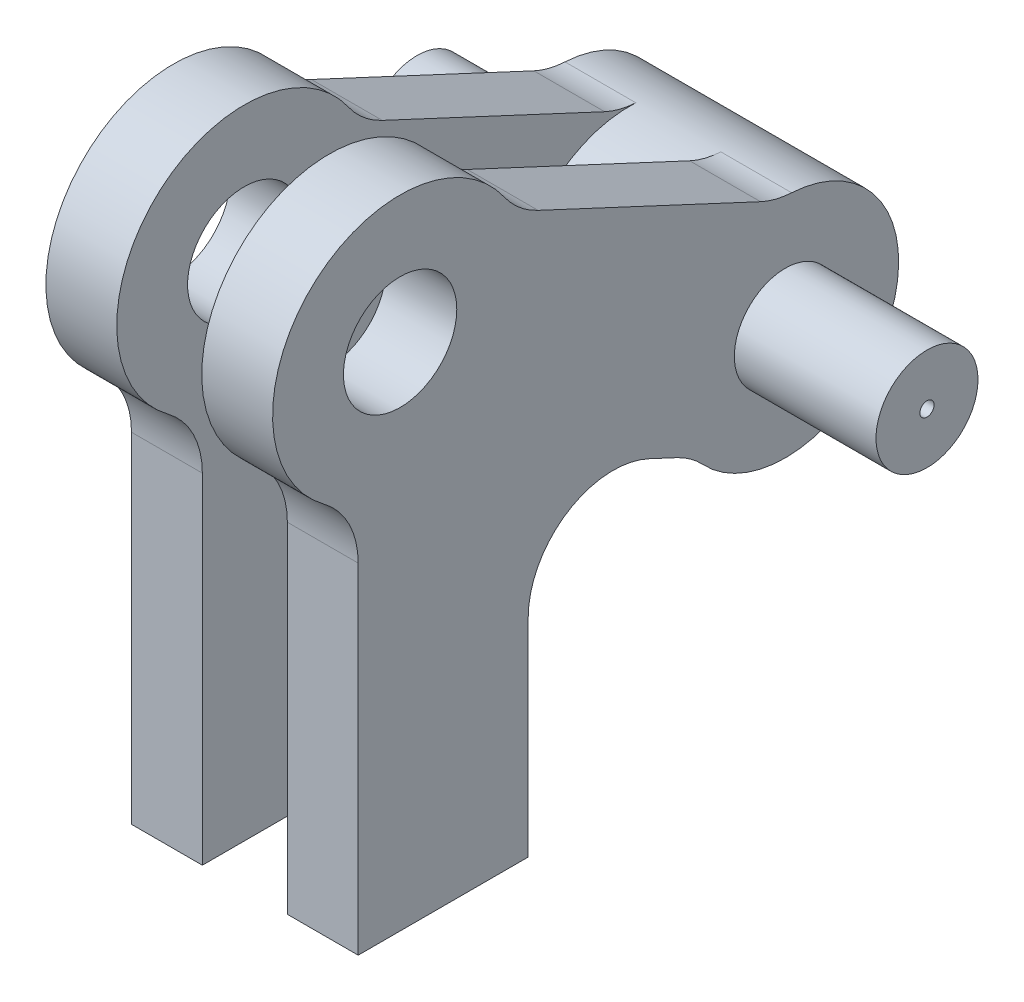
SolidWorks part; units mm, degrees
ref_plane "前视基准面" through (0, 0, 0) normal (0, 0, 1) x (1, 0, 0)
ref_plane "上视基准面" through (0, 0, 0) normal (0, 1, 0) x (1, 0, 0)
ref_plane "右视基准面" through (0, 0, 0) normal (1, 0, 0) x (0, 0, -1)
other "Configuration Table"
sketch "草图1" plane through (0, 0, 0) normal (1, 0, 0) x (0, 0, -1)
  line L1 (-1.4792, -3.1721) -> (4.5208, -3.1721)
  line L2 (-1.4792, -3.1721) -> (-1.4792, -18)
  line L3 (-1.4792, -18) -> (4.5208, -18)
  line L4 (4.5208, -3.1721) -> (4.5208, -18)
  line L5 (-1.4792, -3.1721) -> (12.1155, -9.5114)
  line L6 (-1.4792, -3.1721) -> (1.4792, 3.1721)
  line L7 (1.4792, 3.1721) -> (15.0738, -3.1672)
  line L8 (12.1155, -9.5114) -> (15.0738, -3.1672)
  circle A0 centre (0, 0) radius 4.5
  circle A1 centre (13.5946, -6.3393) radius 4
  circle A2 centre (0, 0) radius 2
  circle A3 centre (13.5946, -6.3393) radius 2
  dimension "D4" = 9
  dimension "D5" = 8
  dimension "D8" = 4
  dimension "D1" = 65
  dimension "D2" = 18
  dimension "D3" = 6
  dimension "D6" = 7
  dimension "D7" = 15
extrude "凸台-拉伸1" add sketch "草图1" along normal blind 2.5 contours L6 L7 L8 L5 | A0 | A1 | L1 L4 L3 L2
extrude "切除-拉伸3" cut sketch "草图1<3>" against normal through all and the other way through all contours A2 | A3
sketch "草图1<3>" plane through (0, 0, 0) normal (1, 0, 0) x (0, 0, -1) same geometry as "草图1"
fillet "圆角1" radius 3 5 edges at (1.25, -4.2499, 1.4792) (1.25, 1.9767, -4.0426) (1.25, -5.9699, -4.5208) (1.25, -8.693, -10.3604) (1.25, -2.3488, -13.3187)
extrude "凸台-拉伸2" add sketch "草图1<4>" against normal blind 1.5 contours A3 L8 L5 A1 L7 | A3 L8 L7 A1 L5 region at (0, -3.4938, -16.2502) region at (0, -5.4629, -11.7152)
sketch "草图1<4>" plane through (0, 0, 0) normal (1, 0, 0) x (0, 0, -1) same geometry as "草图1"
extrude "凸台-拉伸5" add sketch "草图1<5>" along normal up to surface (2.5 mm away) contours L8 A3 | L8 A3 region at (0, -6.698, -14.3639) region at (0, -5.9805, -12.8253) up to face at (2.5, 0, -2)
sketch "草图1<5>" plane through (0, 0, 0) normal (1, 0, 0) x (0, 0, -1) same geometry as "草图1"
sketch "草图2" plane through (2.5, 0, 0) normal (1, 0, 0) x (0, 0, -1)
  circle A0 centre (13.5946, -6.3393) radius 2
  circle A1 centre (13.5946, -6.3393) radius 2 construction
  circle A2 centre (13.5946, -6.3393) radius 1.8
  dimension "D1" = 3.6
extrude "凸台-拉伸4" add sketch "草图2" along normal blind 5 contours A2 region at (2.5, -6.3393, -13.5946)
sketch "草图3" plane through (7.5, 0, 0) normal (1, 0, 0) x (0, 0, -1)
  circle A0 centre (13.5946, -6.3393) radius 0.25
  dimension "D1" = 0.5
extrude "切除-拉伸4" cut sketch "草图3" against normal blind 2
ref_plane "基准面1" through (-1.5, 0, 0) normal (-1, 0, 0) x (0, 0, 1)
mirror "镜向1" about plane through (-1.5, 0, 0) normal (-1, 0, 0) of bodies 116 110
equation "\"JointPoint\"= 2mm"
